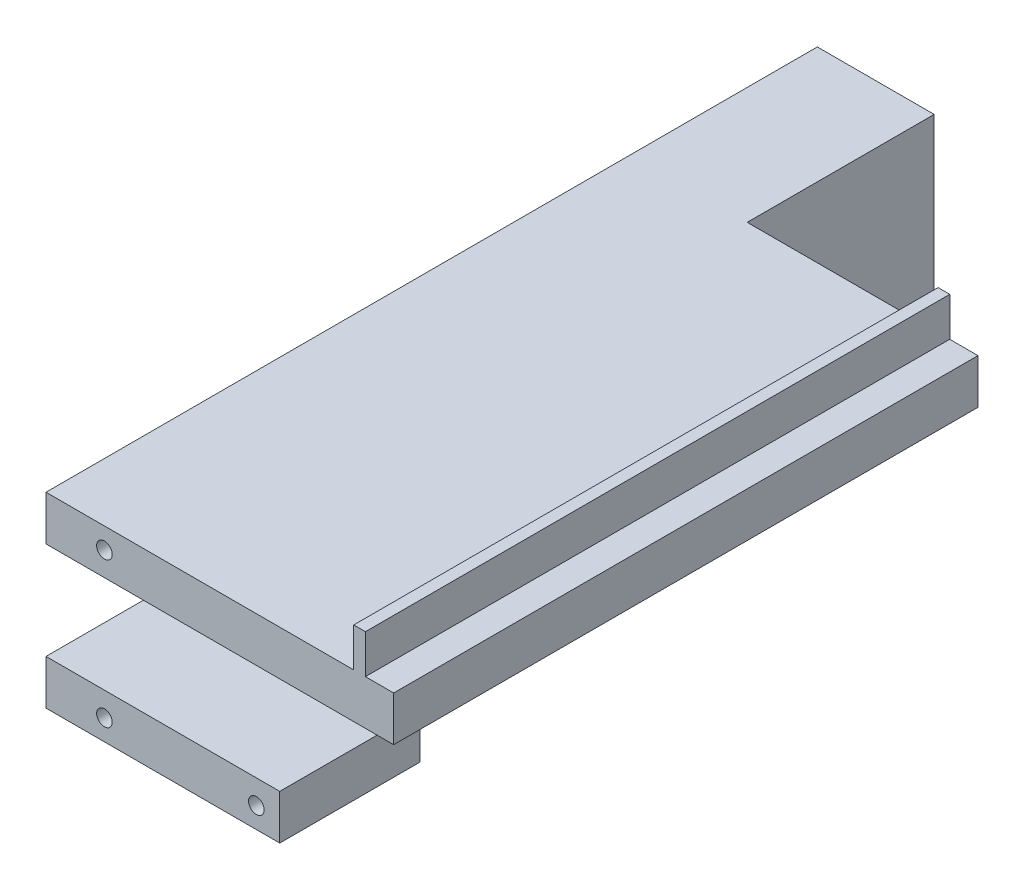
SolidWorks part; units mm, degrees
ref_plane "Alzado" through (0, 0, 0) normal (0, 0, 1) x (1, 0, 0)
ref_plane "Planta" through (0, 0, 0) normal (0, 1, 0) x (1, 0, 0)
ref_plane "Vista lateral" through (0, 0, 0) normal (1, 0, 0) x (0, 0, -1)
sketch "Croquis1" plane through (0, 0, 0) normal (0, 0, 1) x (1, 0, 0)
  line L1 (-66.2162, 31.0113) -> (-6.2162, 31.0113)
  line L2 (-66.2162, 31.0113) -> (-66.2162, -16.9887)
  line L3 (-66.2162, -16.9887) -> (-6.2162, -16.9887)
  line L4 (-6.2162, 31.0113) -> (-6.2162, -16.9887)
  dimension "D1" = 48
  dimension "D2" = 60
extrude "Saliente-Extruir1" add sketch "Croquis1" along normal blind 6
sketch "Croquis4" plane through (0, 0, 6) normal (0, 0, 1) x (1, 0, 0)
  line L0 (-66.2162, 31.0113) -> (-66.2162, 19.5113)
  line L1 (-66.2162, 31.0113) -> (-66.2162, -16.9887) construction
  line L3 (-66.2162, -5.4887) -> (-66.2162, -16.9887)
  line L4 (-66.2162, 31.0113) -> (-6.2162, 31.0113)
  line L6 (-6.2162, 31.0113) -> (-6.2162, 19.5113)
  line L7 (-6.2162, -16.9887) -> (-6.2162, 31.0113) construction
  line L8 (-6.2162, 19.5113) -> (-66.2162, 19.5113)
  line L9 (-66.2162, -5.4887) -> (-6.2162, -5.4887)
  line L10 (-6.2162, -5.4887) -> (-6.2162, -16.9887)
  line L11 (-6.2162, -16.9887) -> (-66.2162, -16.9887)
  dimension "D1" = 25
extrude "Saliente-Extruir3" add sketch "Croquis4" along normal blind 30
sketch "Croquis3" plane through (0, 0, 6) normal (0, 0, 1) x (1, 0, 0)
  circle A0 centre (-51.2162, 25.6613) radius 2.125
  circle A1 centre (-12.2162, 25.6613) radius 2.125
  circle A2 centre (-12.2162, -11.6387) radius 2.125
  circle A3 centre (-51.2162, -11.6387) radius 2.125
  dimension "D7" = 4.25
  dimension "D9" = 4.25
  dimension "D10" = 4.25
  dimension "D2" = 4.25
  dimension "D3" = 37.3
  dimension "D4" = 39
sketch "Croquis5" plane through (0, 0, 36) normal (0, 0, 1) x (1, 0, 0)
  circle A0 centre (-51.2162, 25.6613) radius 2
  circle A1 centre (-12.2162, 25.6613) radius 2
  circle A2 centre (-12.2162, -11.6387) radius 2
  circle A3 centre (-51.2162, -11.6387) radius 2
  dimension "D1" = 4
  dimension "D2" = 4
  dimension "D3" = 4
  dimension "D4" = 4
extrude "Cortar-Extruir3" cut sketch "Croquis5" against normal blind 16
sketch "Croquis6" plane through (0, 0, 0) normal (0, 0, -1) x (-1, 0, 0)
  line L0 (66.2162, -16.9887) -> (6.2162, -16.9887) construction
  line L1 (66.2162, 31.0113) -> (36.2162, 31.0113)
  line L2 (66.2162, 31.0113) -> (66.2162, -16.9887)
  line L3 (66.2162, -16.9887) -> (36.2162, -16.9887)
  line L4 (36.2162, 31.0113) -> (36.2162, -16.9887)
  dimension "D1" = 30
extrude "Saliente-Extruir4" add sketch "Croquis6" along normal blind 162
sketch "Croquis7" plane through (0, 0, -162) normal (0, 0, -1) x (-1, 0, 0)
  circle A0 centre (51.2162, 7.0113) radius 2
  dimension "D1" = 4
extrude "Cortar-Extruir4" cut sketch "Croquis7" against normal blind 16
sketch "Croquis8" plane through (0, 0, -162) normal (0, 0, -1) x (-1, 0, 0)
  line L0 (41.2162, 12.0113) -> (41.2162, 9.5131)
  line L10 (36.2162, 12.0113) -> (41.2162, 12.0113)
  line L11 (36.2162, 12.0113) -> (36.2162, 2.0113)
  line L12 (36.2162, 2.0113) -> (41.2162, 2.0113)
  line L21 (41.2162, 9.5131) -> (44.2162, 9.5131)
  line L23 (41.2162, 4.5131) -> (44.2162, 4.5131)
  line L24 (44.2162, 9.5131) -> (44.2162, 4.5131)
  line L25 (41.2162, 2.0113) -> (41.2162, 4.5131)
  dimension "D1" = 5
  dimension "D2" = 3
  dimension "D3" = 5
sketch "Croquis11" plane through (-36.2162, 0, 0) normal (1, 0, 0) x (0, 0, -1)
  line L1 (-36, 19.5113) -> (-36, 31.0113) construction
  line L4 (-36, 19.5113) -> (-36, 31.0113)
  line L6 (-36, 19.5113) -> (114, 19.5113)
  line L7 (114, 19.5113) -> (114, 31.0113)
  line L8 (162, 31.0113) -> (0, 31.0113) construction
  line L9 (162, 31.0113) -> (0, 31.0113) construction
  line L10 (-36, 31.0113) -> (114, 31.0113)
  dimension "D1" = 150
extrude "Saliente-Extruir6" add sketch "Croquis11" along normal blind 59.25
sketch "Croquis12" plane through (0, 31.0113, 0) normal (0, 1, 0) x (1, 0, 0)
  line L0 (23.0338, -36) -> (-66.2162, -36) construction
  line L1 (15.7838, -36) -> (12.7838, -36)
  line L2 (-66.2162, -36) -> (-66.2162, 162) construction
  line L3 (-66.2162, -36) -> (-66.2162, 162) construction
  line L4 (15.7838, -36) -> (15.7838, 114)
  line L5 (15.7838, 114) -> (12.7838, 114)
  line L6 (23.0338, 114) -> (-36.2162, 114) construction
  line L7 (12.7838, 114) -> (12.7838, -36)
  dimension "D1" = 82
  dimension "D2" = 150
  dimension "D3" = 3
extrude "Saliente-Extruir7" add sketch "Croquis12" along normal blind 10
